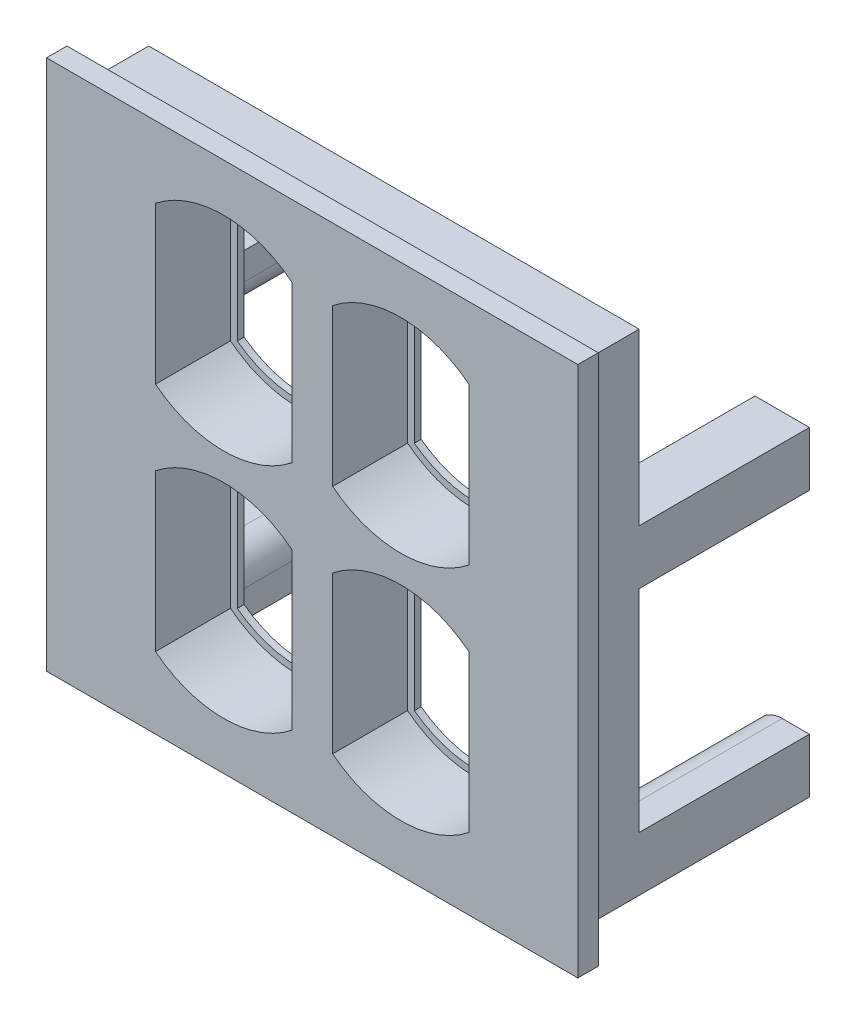
SolidWorks part; units mm, degrees
material "ABS-White"
ref_plane "Front Plane" through (0, 0, 0) normal (0, 0, 1) x (1, 0, 0)
ref_plane "Top Plane" through (0, 0, 0) normal (0, 1, 0) x (1, 0, 0)
ref_plane "Right Plane" through (0, 0, 0) normal (1, 0, 0) x (0, 0, -1)
sketch "Sketch1" plane through (0, 0, 0) normal (0, 0, 1) x (1, 0, 0)
  line L1 (-36, -36) -> (36, -36)
  line L2 (-36, -36) -> (-36, 36)
  line L3 (-36, 36) -> (36, 36)
  line L4 (36, -36) -> (36, 36)
  line L5 (-36, -36) -> (36, 36) construction
  line L6 (-36, 36) -> (36, -36) construction
  point P0 (0, 0)
  dimension "D1" = 72
  dimension "D2" = 72
extrude "Boss-Extrude1" add sketch "Sketch1" along normal blind 12
sketch "Sketch20" plane through (0, -36, 0) normal (0, -1, 0) x (1, 0, 0)
  line L0 (28, 5) -> (-28, 5) construction
  line L1 (0, 0) -> (0, 5) construction
  line L2 (-36, 0) -> (36, 0) construction
  line L3 (-36, 12) -> (36, 12) construction
  circle A0 centre (-28, 5) radius 1.25
  circle A1 centre (28, 5) radius 1.25
  dimension "D1" = 2.5
  dimension "D2" = 7
  dimension "D3" = 56
extrude "Cut-Extrude7" cut sketch "Sketch20" against normal blind 10
sketch "Sketch2" plane through (0, 0, 12) normal (0, 0, 1) x (1, 0, 0)
  line L0 (-13, 32) -> (-13, 2) construction
  line L2 (-23, 5.5) -> (-23, 28.5)
  line L4 (-3, 5.5) -> (-3, 28.5)
  line L5 (-23, 5.5) -> (-3, 28.5) construction
  line L6 (-23, 28.5) -> (-3, 5.5) construction
  arc A0 (-23, 28.5) -> (-3, 28.5) centre (-13, 15.9643) cw
  arc A1 (-23, 5.5) -> (-3, 5.5) centre (-13, 18.0357) ccw
  point P0 (-13, 17)
  dimension "D5" = 30
  dimension "D1" = 13
  dimension "D2" = 17
  dimension "D3" = 23
  dimension "D4" = 20
extrude "Cut-Extrude1" cut sketch "Sketch2" against normal offset from surface (11 mm away) 1 up to face at (0, 0, 0)
sketch "Sketch4" plane through (0, 0, 1) normal (0, 0, 1) x (1, 0, 0)
  line L4 (-4, 5.9911) -> (-4, 28.0089)
  line L5 (-22, 28.0089) -> (-22, 5.9911)
  line L6 (-4, 5.9911) -> (-4, 28.0089)
  line L7 (-22, 28.0089) -> (-22, 5.9911)
  arc A4 (-22, 5.9911) -> (-4, 5.9911) centre (-13, 18.0357) ccw
  arc A5 (-4, 28.0089) -> (-22, 28.0089) centre (-13, 15.9643) ccw
  arc A6 (-22, 5.9911) -> (-4, 5.9911) centre (-13, 18.0357) ccw
  arc A7 (-4, 28.0089) -> (-22, 28.0089) centre (-13, 15.9643) ccw
  dimension "D1" = 1
extrude "Cut-Extrude2" cut sketch "Sketch4" against normal through all
mirror "Mirror2" about plane through (0, 0, 0) normal (0, 1, 0) of "Cut-Extrude2", "Cut-Extrude1"
mirror "Mirror3" about plane through (0, 0, 0) normal (1, 0, 0) of "Mirror2"
fillet "Fillet1" [suppressed] radius 8
sketch "Sketch5" [suppressed] plane through (0, 0, 12) normal (0, 0, 1) x (1, 0, 0)
  line L0 (-33.5, 25.5) -> (-33.5, -25.5) construction
  line L1 (-25.5, -33.5) -> (25.5, -33.5) construction
  line L2 (33.5, -25.5) -> (33.5, 25.5) construction
  line L3 (25.5, 33.5) -> (-25.5, 33.5) construction
  line L4 (-33.5, 25.5) -> (-33.5, -25.5)
  line L5 (-25.5, -33.5) -> (25.5, -33.5)
  line L6 (33.5, -25.5) -> (33.5, 25.5)
  line L7 (25.5, 33.5) -> (-25.5, 33.5)
  arc A0 (-33.5, -25.5) -> (-25.5, -33.5) centre (-25.5, -25.5) ccw construction
  arc A1 (25.5, -33.5) -> (33.5, -25.5) centre (25.5, -25.5) ccw construction
  arc A2 (33.5, 25.5) -> (25.5, 33.5) centre (25.5, 25.5) ccw construction
  arc A3 (-25.5, 33.5) -> (-33.5, 25.5) centre (-25.5, 25.5) ccw construction
  arc A4 (-33.5, -25.5) -> (-25.5, -33.5) centre (-25.5, -25.5) ccw
  arc A5 (25.5, -33.5) -> (33.5, -25.5) centre (25.5, -25.5) ccw
  arc A6 (33.5, 25.5) -> (25.5, 33.5) centre (25.5, 25.5) ccw
  arc A7 (-25.5, 33.5) -> (-33.5, 25.5) centre (-25.5, 25.5) ccw
extrude "Extrude-Thin1" [suppressed] add sketch "Sketch5" along normal blind 17 thin thin type one direction reverse wall 1
sketch "Sketch6" plane through (0, 0, 0) normal (0, 0, -1) x (-1, 0, 0)
  line L0 (36, 36) -> (-36, 36)
  line L1 (-36, 36) -> (36, 36) construction
  line L2 (-36, 36) -> (-36, 21)
  line L3 (-36, -36) -> (-36, 36) construction
  line L4 (-36, 21) -> (-33, 21)
  line L5 (-33, 21) -> (-33, 33)
  line L6 (-33, 33) -> (33, 33)
  line L7 (33, 33) -> (33, 21)
  line L8 (33, 21) -> (36, 21)
  line L9 (36, 36) -> (36, -36) construction
  line L10 (36, 21) -> (36, 36)
  dimension "D1" = 3
  dimension "D2" = 3
  dimension "D4" = 15
extrude "Boss-Extrude2" [suppressed] add sketch "Sketch6" along normal blind 15
sketch "Sketch8" plane through (0, 0, 12) normal (0, 0, 1) x (1, 0, 0)
  line L10 (36, -36) -> (36, 36) construction
  line L11 (36, 36) -> (-36, 36) construction
  line L12 (-36, 36) -> (-36, -36) construction
  line L13 (-36, -36) -> (36, -36) construction
  line L14 (-39, -39) -> (39, -39)
  line L15 (-39, 39) -> (-39, -39)
  line L16 (39, 39) -> (-39, 39)
  line L17 (39, -39) -> (39, 39)
  line L18 (-39, -39) -> (39, -39)
  line L19 (-39, 39) -> (-39, -39)
  line L20 (39, 39) -> (-39, 39)
  line L21 (39, -39) -> (39, 39)
  line L22 (36, -36) -> (36, 36)
  line L23 (36, 36) -> (-36, 36)
  line L24 (-36, 36) -> (-36, -36)
  line L25 (-36, -36) -> (36, -36)
  dimension "D1" = 3
extrude "Boss-Extrude3" add sketch "Sketch8" against normal blind 3
sketch "Sketch22" plane through (0, 0, 0) normal (0, 0, -1) x (-1, 0, 0)
  line L0 (-36, -36) -> (-36, 36) construction
  line L1 (-36, -36) -> (-28, -36)
  line L2 (-36, -36) -> (-36, -28)
  line L3 (-36, -28) -> (-28, -28)
  line L4 (-28, -36) -> (-28, -28)
  line L5 (-36, 11) -> (-28, 11)
  line L6 (-36, 11) -> (-36, 3)
  line L7 (-36, 3) -> (-28, 3)
  line L8 (-28, 11) -> (-28, 3)
  line L9 (-36, 7) -> (-36, -32) construction
  dimension "D1" = 8
  dimension "D2" = 39
extrude "Boss-Extrude4" add sketch "Sketch22" along normal blind 25
fillet "Fillet2" radius 4 2 edges at (28, -28, -12.5) (28, 3, -12.5)
sketch "Sketch23" plane through (0, 0, -25) normal (0, 0, -1) x (-1, 0, 0)
  line L0 (-36, -28) -> (-36, -36) construction
  line L1 (-36, -36) -> (-28, -36) construction
  circle A0 centre (-32, -32) radius 1.25
  circle A1 centre (-32, 7) radius 1.25
  dimension "D3" = 2.5
  dimension "D1" = 4
  dimension "D2" = 4
  dimension "D4" = 39
extrude "Cut-Extrude8" cut sketch "Sketch23" against normal blind 10
mirror "Mirror4" about plane through (0, 0, 0) normal (1, 0, 0) of "Fillet2", "Cut-Extrude8", "Boss-Extrude4"
